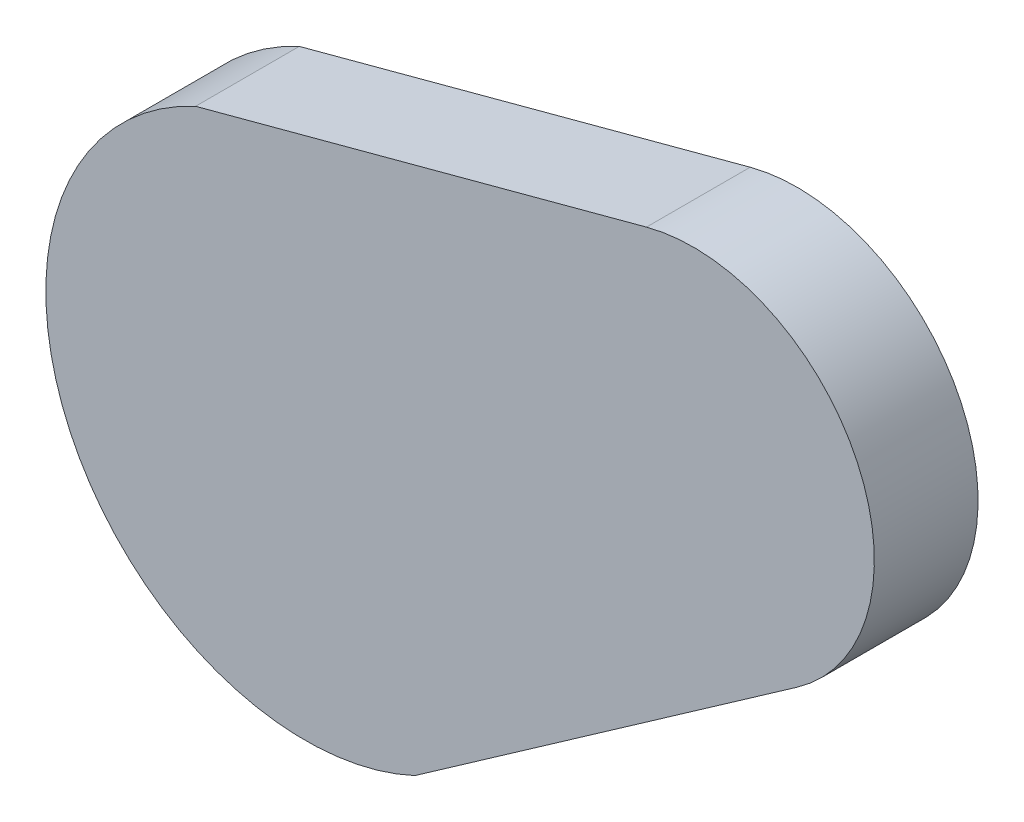
SolidWorks part; units mm, degrees
ref_plane "前视基准面" through (0, 0, 0) normal (0, 0, 1) x (1, 0, 0)
ref_plane "上视基准面" through (0, 0, 0) normal (0, 1, 0) x (1, 0, 0)
ref_plane "右视基准面" through (0, 0, 0) normal (1, 0, 0) x (0, 0, -1)
sketch "草图3" plane through (0, 0, 10) normal (0, 0, 1) x (1, 0, 0)
  line L0 (-49.8893, -80) -> (73.6733, -80) construction
  line L1 (0, -129.5009) -> (0, -43.5196) construction
  line L2 (-10.5655, -57.3423) -> (32.9012, -45.6954)
  line L3 (-10.5655, -57.3423) -> (10.5655, -102.6577) construction
  line L4 (-22.6577, -90.5655) -> (29.4261, -66.2784) construction
  line L5 (10.5655, -102.6577) -> (47.4273, -76.8468)
  arc A0 (10.5655, -102.6577) -> (-10.5655, -57.3423) centre (0, -80) cw
  arc A2 (47.4273, -76.8468) -> (32.9012, -45.6954) centre (37.4178, -62.5518) ccw
  dimension "D1" = 25
  dimension "D4" = 17.451
  dimension "D5" = 25
  dimension "D6" = 80
  dimension "D2" = 80
  dimension "D3" = 45
extrude "凸台-拉伸3" add sketch "草图3" along normal blind 10
